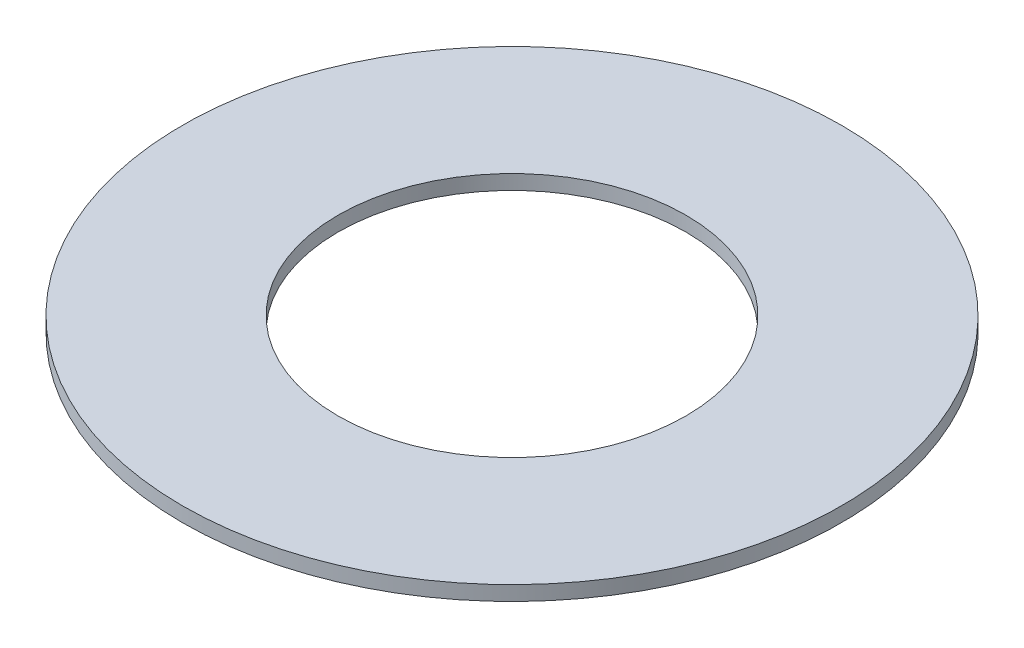
SolidWorks part; units mm, degrees
ref_plane "Front Plane" through (0, 0, 0) normal (0, 0, 1) x (1, 0, 0)
ref_plane "Top Plane" through (0, 0, 0) normal (0, 1, 0) x (1, 0, 0)
ref_plane "Right Plane" through (0, 0, 0) normal (1, 0, 0) x (0, 0, -1)
sketch "Sketch1" plane through (0, 0, 0) normal (0, 1, 0) x (1, 0, 0)
  circle A0 centre (0, 0) radius 90
  dimension "FLANGE_OD" = 180
extrude "Boss-Extrude1" add sketch "Sketch1" along normal blind 4
sketch "Sketch2" plane through (0, 0, 0) normal (0, 1, 0) x (1, 0, 0)
  circle A0 centre (0, 0) radius 47.5
  dimension "BORE_D" = 95
extrude "Cut-Extrude1" cut sketch "Sketch2" along normal through all
sketch "Sketch3" plane through (0, 4, 0) normal (0, 1, 0) x (1, 0, 0)
  circle A0 centre (0, 0) radius 33.9255 construction
  circle A1 centre (-33.9255, 0) radius 5.3696
  dimension "BOLT_D" = 10.7392
  dimension "BOLT_PCD" = 67.8511
extrude "Cut-Extrude2" cut sketch "Sketch3" against normal blind 3.0841 rebuild error yes
pattern_circular "CirPattern1" count 6 over 360 rebuild error yes
